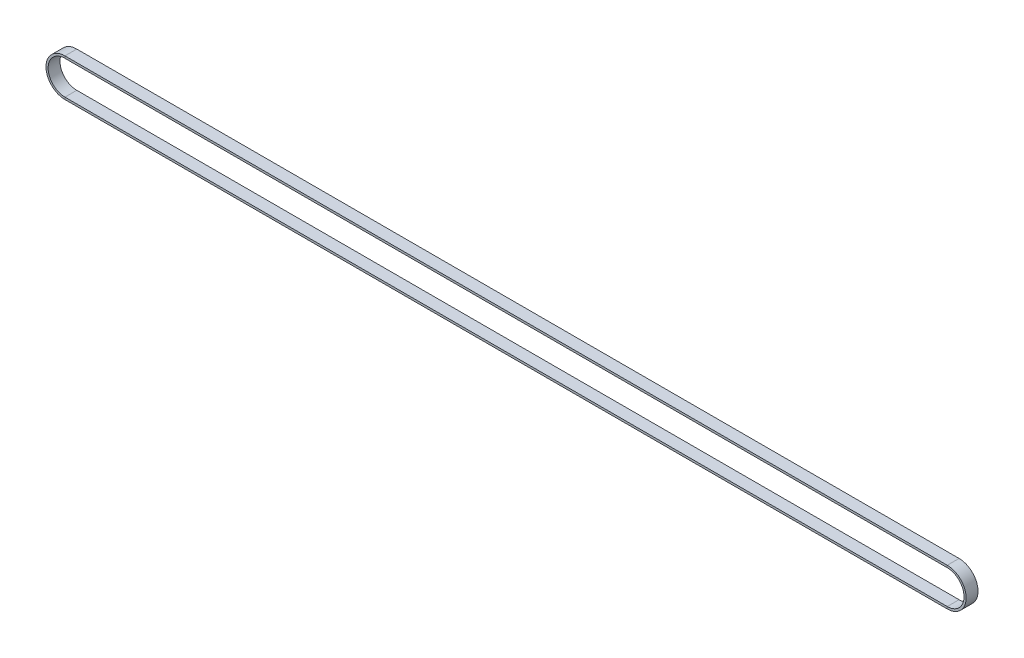
SolidWorks part; units mm, degrees
ref_plane "Front Plane" through (0, 0, 0) normal (0, 0, 1) x (1, 0, 0)
ref_plane "Top Plane" through (0, 0, 0) normal (0, 1, 0) x (1, 0, 0)
ref_plane "Right Plane" through (0, 0, 0) normal (1, 0, 0) x (0, 0, -1)
sketch "Sketch2" plane through (0, 0, 0) normal (0, 0, 1) x (1, 0, 0)
  line L0 (0, 0) -> (1, 0) construction
  line L1 (0, 0) -> (0, 1) construction
  line L2 (17.4625, 3.8013) -> (491.0039, 3.8013)
  line L3 (491.0039, -16.5187) -> (17.4625, -16.5187)
  arc A0 (17.4625, -16.5187) -> (17.4625, 3.8013) centre (17.4625, -6.3587) cw
  arc A1 (491.0039, 3.8013) -> (491.0039, -16.5187) centre (491.0039, -6.3587) cw
ref_plane "Plane1" through (0, 0, 0) normal (0, 0, 1) x (1, 0, 0)
ref_plane "Plane2" through (17.4625, 3.8013, 0) normal (1, 0, 0) x (0, 0, -1)
sketch "Sketch3" plane through (17.4625, 3.8013, 0) normal (1, 0, 0) x (0, 0, -1)
  line L0 (0, 0) -> (0, -1.143) construction
  line L1 (0, 0) -> (0, -20.32) construction
  line L2 (0, 0) -> (0, -20.32) construction
  line L3 (-3.175, -1.143) -> (3.175, -1.143)
  line L4 (3.175, -1.143) -> (3.175, 0)
  line L5 (3.175, 0) -> (-3.175, 0)
  line L6 (-3.175, -1.143) -> (-3.175, 0)
  dimension "D1" = 6.35
  dimension "D2" = 1.143
sweep "Sweep1" add profiles "Sketch3" path "Sketch2"
